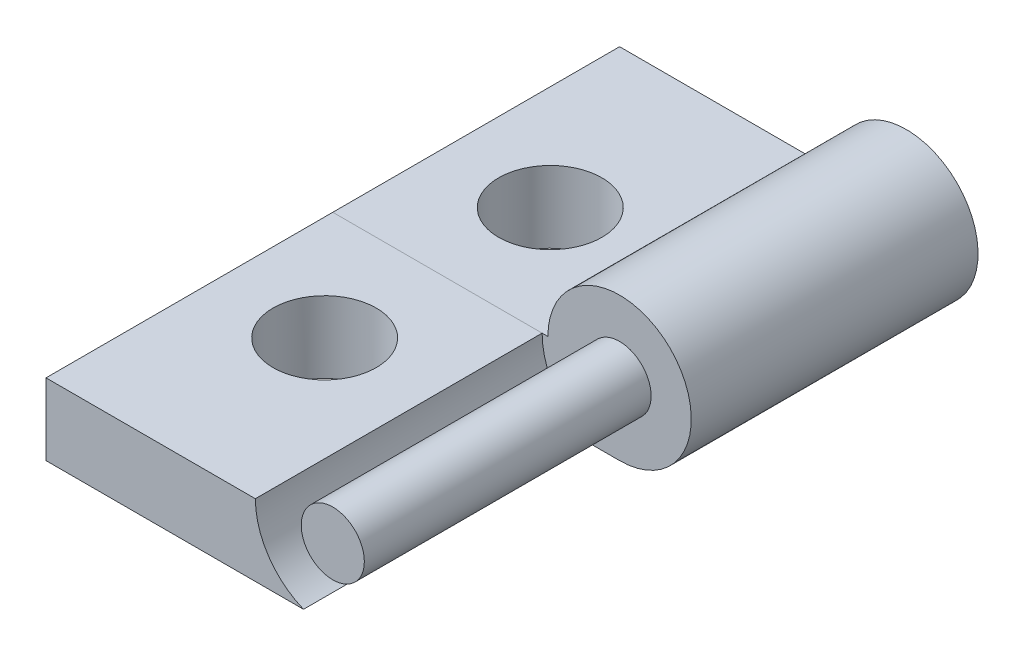
SolidWorks part; units mm, degrees
ref_plane "Front Plane" through (0, 0, 0) normal (0, 0, 1) x (1, 0, 0)
ref_plane "Top Plane" through (0, 0, 0) normal (0, 1, 0) x (1, 0, 0)
ref_plane "Right Plane" through (0, 0, 0) normal (1, 0, 0) x (0, 0, -1)
sketch "Sketch1" plane through (0, 0, 0) normal (0, 0, 1) x (1, 0, 0)
  line L1 (0, 0) -> (12.7, 0)
  line L2 (0, 0) -> (0, 3.175)
  line L3 (0, 3.175) -> (9.525, 3.175)
  arc A0 (12.7, 0) -> (9.525, 3.175) centre (12.7, 3.175) ccw
  dimension "D1" = 12.7
  dimension "D2" = 3.175
extrude "Boss-Extrude1" add sketch "Sketch1" along normal blind 12.7
sketch "Sketch3" plane through (0, 0, 12.7) normal (0, 0, 1) x (1, 0, 0)
  line L0 (9.2709, 3.175) -> (0, 3.175)
  line L1 (0, 3.175) -> (0, 0)
  line L2 (0, 0) -> (11.4046, 0)
  line L3 (12.6751, 0) -> (12.7, 0)
  arc A1 (9.2709, 3.175) -> (11.4046, 0) centre (12.7, 3.175) ccw
  circle A2 centre (12.7, 3.175) radius 1.397
  line M1 (0, 3.175) -> (0, 0)
  line M2 (0, 0) -> (12.7, 0)
  dimension "D1" = 2.794
extrude "Boss-Extrude2" add sketch "Sketch3" along normal blind 12.7 contours A1 L0 M1 M2 | A2 region at (4.9476, 1.5366, 12.7) region at (12.7, 3.175, 12.7)
sketch "Sketch4" plane through (0, 3.175, 0) normal (0, 1, 0) x (1, 0, 0)
  line L0 (4.6355, -5.4187) -> (4.6355, 0) construction
  line L1 (9.525, 0) -> (0, 0) construction
  line L2 (4.6355, -9.9907) -> (4.6355, -15.4093) construction
  line L3 (4.6355, -19.9813) -> (4.6355, -25.4) construction
  line L4 (9.2709, -25.4) -> (0, -25.4) construction
  line L5 (6.9215, -17.6953) -> (9.2709, -17.6953) construction
  line L6 (9.2709, -25.4) -> (9.2709, -12.7) construction
  line L7 (2.3495, -17.6953) -> (0, -17.6953) construction
  line L8 (0, -25.4) -> (0, -12.7) construction
  circle A0 centre (4.6355, -7.7047) radius 2.286
  circle A1 centre (4.6355, -17.6953) radius 2.286
  dimension "D1" = 4.572
  dimension "D2" = 4.572
extrude "Cut-Extrude1" cut sketch "Sketch4" against normal blind 12.7
